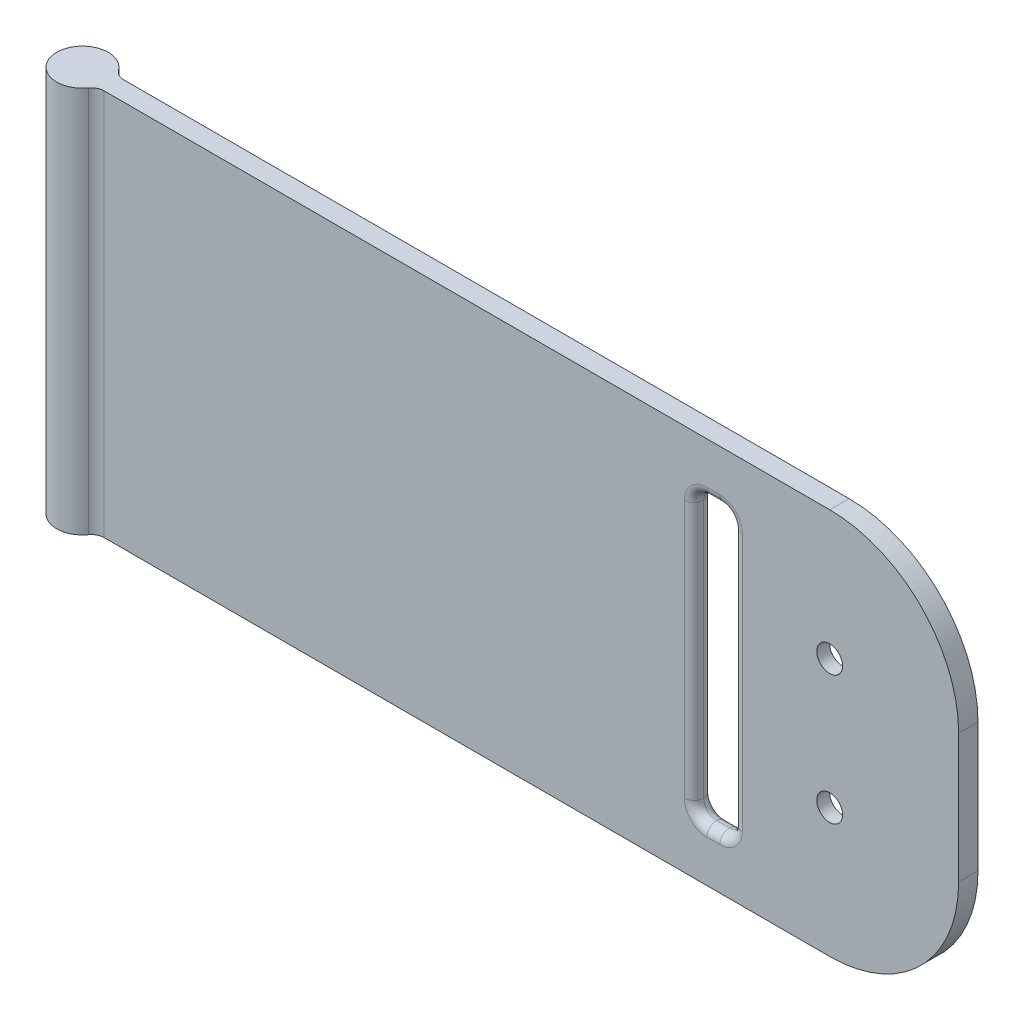
SolidWorks part; units mm, degrees
material "Silicon Rubber"
ref_plane "Front Plane" through (0, 0, 0) normal (0, 0, 1) x (1, 0, 0)
ref_plane "Top Plane" through (0, 0, 0) normal (0, 1, 0) x (1, 0, 0)
ref_plane "Right Plane" through (0, 0, 0) normal (1, 0, 0) x (0, 0, -1)
sketch "Sketch1" plane through (0, 0, 0) normal (0, 1, 0) x (1, 0, 0)
  line L0 (0, 0) -> (2.4367, 0) construction
  line L1 (2.4367, 1.75) -> (2.4367, -1.75) construction
  line L2 (2.4367, 0.75) -> (2.4367, -0.75) construction
  line L3 (2.4367, 0.75) -> (68.6835, 0.75)
  line L4 (68.6835, 0.75) -> (68.6835, -0.75)
  line L5 (68.6835, -0.75) -> (2.4367, -0.75)
  circle A0 centre (0, 0) radius 2 construction
  arc A1 (2.4367, 0.75) -> (1.6245, 1.1667) centre (2.4367, 1.75) cw
  arc A2 (2.4367, -0.75) -> (1.6245, -1.1667) centre (2.4367, -1.75) ccw
  arc A3 (1.6245, 1.1667) -> (1.6245, -1.1667) centre (0, 0) ccw
  point P6 (2.4367, 0)
  point P9 (2.4367, 0)
  dimension "D1" = 4
  dimension "D2" = 1.5
  dimension "D3" = 3.5
  dimension "D4" = 66.2468
extrude "Boss-Extrude1" add sketch "Sketch1" along normal blind 30
sketch "Sketch2" plane through (0, 0, 0.75) normal (0, 0, 1) x (1, 0, 0)
  line L0 (2.4367, 30) -> (2.4367, 0) construction
  line L1 (48.1645, 4) -> (51.1645, 4)
  line L2 (48.1645, 4) -> (48.1645, 26)
  line L3 (48.1645, 26) -> (51.1645, 26)
  line L4 (51.1645, 4) -> (51.1645, 26)
  line L5 (48.1645, 4) -> (51.1645, 26) construction
  line L6 (48.1645, 26) -> (51.1645, 4) construction
  line L7 (2.4367, 0) -> (68.6835, 0) construction
  point P0 (49.6645, 15)
  dimension "D1" = 47.2278
  dimension "D2" = 3
  dimension "D3" = 15
  dimension "D4" = 22
extrude "Cut-Extrude1" cut sketch "Sketch2" against normal through all
fillet "Fillet2" radius 10 2 edges at (68.6835, 0, 0) (68.6835, 30, 0)
sketch "Sketch5" plane through (0, 0, -0.75) normal (0, 0, -1) x (-1, 0, 0)
  circle A0 centre (-58.6835, 20) radius 2
  circle A1 centre (-58.6835, 10) radius 2
  dimension "D1" = 4
  dimension "D2" = 4
extrude "Cut-Extrude2" cut sketch "Sketch5" against normal blind 0.5
sketch "Sketch8" plane through (0, 0, -0.25) normal (0, 0, -1) x (-1, 0, 0)
  circle A0 centre (-58.6835, 20) radius 1
  circle A1 centre (-58.6835, 10) radius 1
  dimension "D1" = 2
  dimension "D2" = 2
extrude "Cut-Extrude3" cut sketch "Sketch8" against normal through all
fillet "Fillet3" radius 1 4 edges at (48.1645, 4, 0) (51.1645, 4, 0) (48.1645, 26, 0) (51.1645, 26, 0)
fillet "Fillet4" radius 0.75 16 edges at (48.4574, 25.7071, 0.75) (49.6645, 26, 0.75) (50.8716, 25.7071, 0.75) (51.1645, 15, 0.75) (50.8716, 4.2929, 0.75) (49.6645, 4, 0.75) (48.4574, 4.2929, 0.75) (48.4574, 25.7071, -0.75) (49.6645, 26, -0.75) (50.8716, 25.7071, -0.75) (51.1645, 15, -0.75) (50.8716, 4.2929, -0.75) (49.6645, 4, -0.75) (48.4574, 4.2929, -0.75) (48.1645, 15, 0.75) (48.1645, 15, -0.75)
